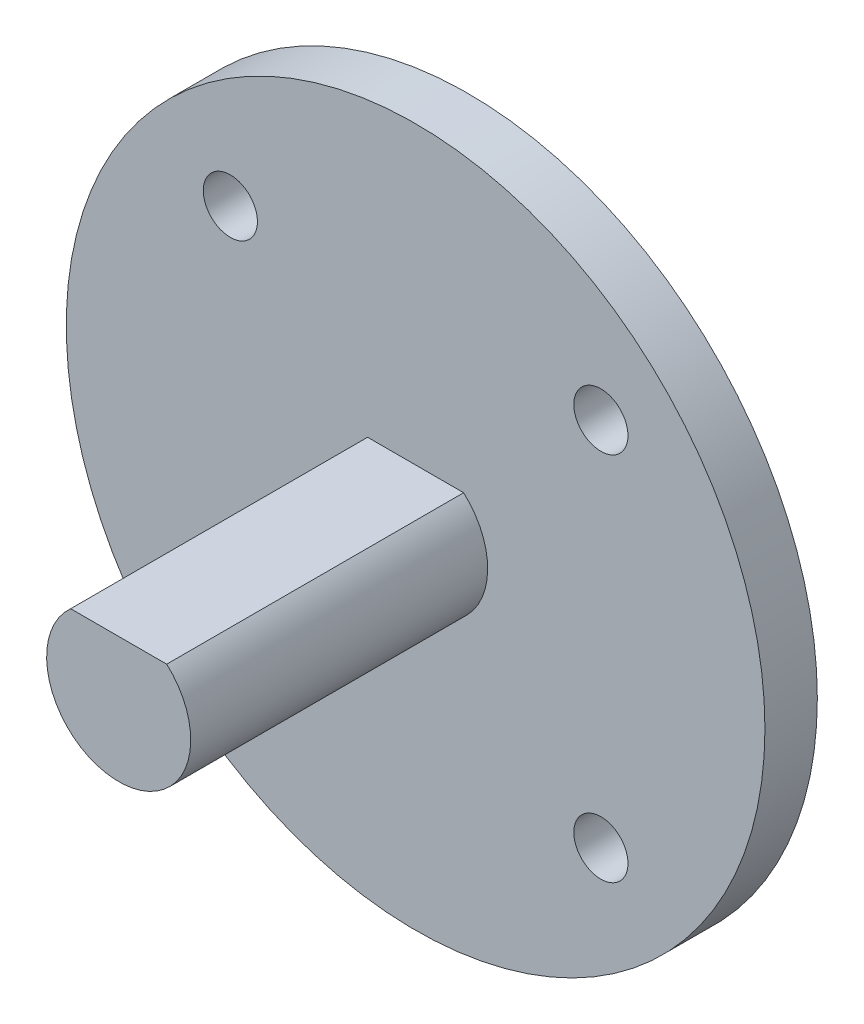
SolidWorks part; units mm, degrees
ref_plane "Front" through (0, 0, 0) normal (0, 0, 1) x (1, 0, 0)
ref_plane "Top" through (0, 0, 0) normal (0, 1, 0) x (1, 0, 0)
ref_plane "Right" through (0, 0, 0) normal (1, 0, 0) x (0, 0, -1)
sketch "Sketch1" plane through (0, 0, 0) normal (0, 0, 1) x (1, 0, 0)
  line L0 (-32.5019, 0) -> (34.1972, 0) construction
  line L1 (-2.7495, 3.075) -> (2.7495, 3.075)
  line L2 (0, 0) -> (10.6066, 10.6066) construction
  circle A0 centre (0, 0) radius 4.125
  circle A1 centre (0, 0) radius 15 construction
  circle A2 centre (0, 0) radius 20
  circle A3 centre (10.6066, 10.6066) radius 1.55
  circle A7 centre (10.6066, -10.6066) radius 1.55
  circle A8 centre (-10.6066, -10.6066) radius 1.55
  circle A9 centre (-10.6066, 10.6066) radius 1.55
  point P17 (0, 0)
  point P18 (0, -4.125)
  point P22 (0, 0)
  dimension "D1" = 8.25
  dimension "D2" = 30
  dimension "D3" = 40
  dimension "D4" = 3.1
  dimension "D5" = 45
  dimension "D6" = 7.2
  dimension "D7" = 4
extrude "Boss-Extrude1" add sketch "Sketch1" along normal blind 3 contours A2 A3 A0 | L1 A0 region at (0, 3.4999, 0) region at (-19.4343, 0, 0)
sketch "Sketch2" plane through (0, 0, 0) normal (0, 1, 0) x (1, 0, 0)
  line L0 (-8.7796, -1.5) -> (9.9295, -1.5) construction
  line L1 (-20, -3) -> (20, -3) construction
  line L2 (-2.7495, 0) -> (2.7495, 0) construction
  circle A0 centre (0, -1.5) radius 2.05
  dimension "D1" = 4.1
extrude "Cut-Extrude1" [suppressed] cut sketch "Sketch2" along normal up to next
sketch "Sketch4" plane through (0, 0, 0) normal (0, 0, 1) x (1, 0, 0)
  line L0 (0, 0) -> (5.6569, 5.6569) construction
  line L1 (0, 0) -> (25.843, 0) construction
  circle A0 centre (0, 0) radius 8 construction
  circle A1 centre (5.6569, 5.6569) radius 1.5
  circle A2 centre (5.6569, -5.6569) radius 1.5
  circle A3 centre (-5.6569, -5.6569) radius 1.5
  circle A4 centre (-5.6569, 5.6569) radius 1.5
  point P15 (0, 0)
  dimension "D1" = 16
  dimension "D2" = 3
  dimension "D3" = 45
  dimension "D4" = 4
extrude "Cut-Extrude2" [suppressed] cut sketch "Sketch4" against normal through all both and the other way through all
extrude "Boss-Extrude2" add sketch "Sketch1<3>" along normal blind 20 contours L1 A0 region at (0, -0.28, 0)
sketch "Sketch1<3>" plane through (0, 0, 0) normal (0, 0, 1) x (1, 0, 0) same geometry as "Sketch1"
